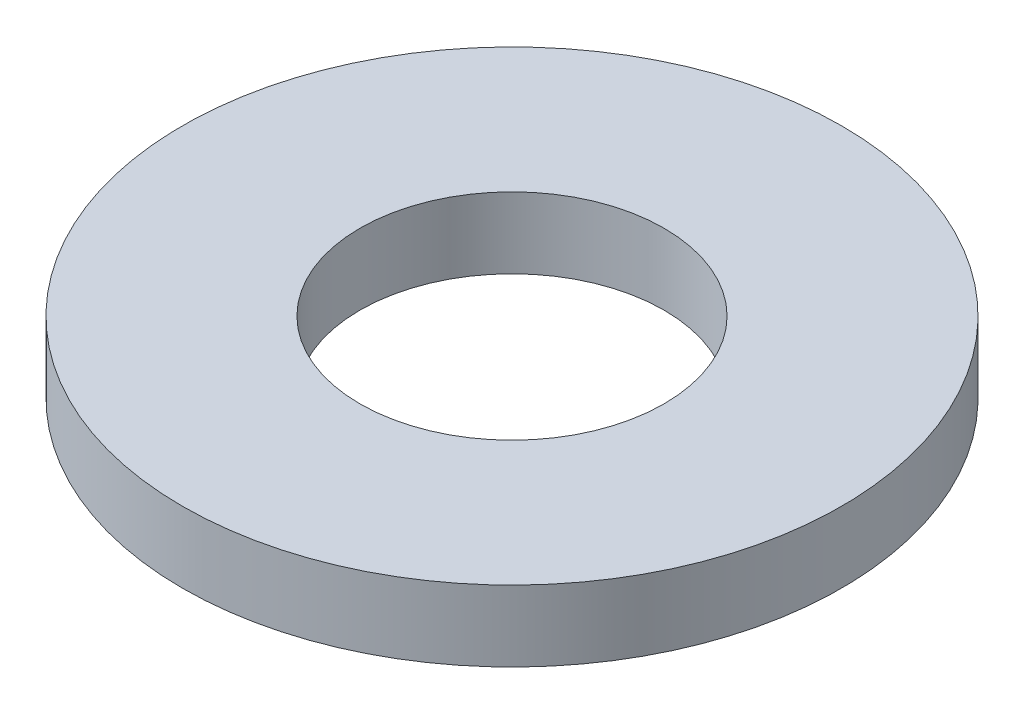
SolidWorks part; units mm, degrees
ref_plane "Front Plane" through (0, 0, 0) normal (0, 0, 1) x (1, 0, 0)
ref_plane "Top Plane" through (0, 0, 0) normal (0, 1, 0) x (1, 0, 0)
ref_plane "Right Plane" through (0, 0, 0) normal (1, 0, 0) x (0, 0, -1)
sketch "Sketch1" plane through (0, 0, 0) normal (0, 1, 0) x (1, 0, 0)
  circle A0 centre (0, 0) radius 65
  dimension "FLANGE_OD" = 130
extrude "Boss-Extrude1" add sketch "Sketch1" along normal blind 14
sketch "Sketch2" plane through (0, 0, 0) normal (0, 1, 0) x (1, 0, 0)
  circle A0 centre (0, 0) radius 30
  dimension "BORE_D" = 60
extrude "Cut-Extrude1" cut sketch "Sketch2" along normal through all
sketch "Sketch3" plane through (0, 14, 0) normal (0, 1, 0) x (1, 0, 0)
  circle A0 centre (0, 0) radius 19.2199 construction
  circle A1 centre (-19.2199, 0) radius 4.2419
  dimension "BOLT_D" = 8.4838
  dimension "BOLT_PCD" = 38.4398
extrude "Cut-Extrude2" cut sketch "Sketch3" against normal blind 12.4362 rebuild error yes
pattern_circular "CirPattern1" count 6 over 360 rebuild error yes
